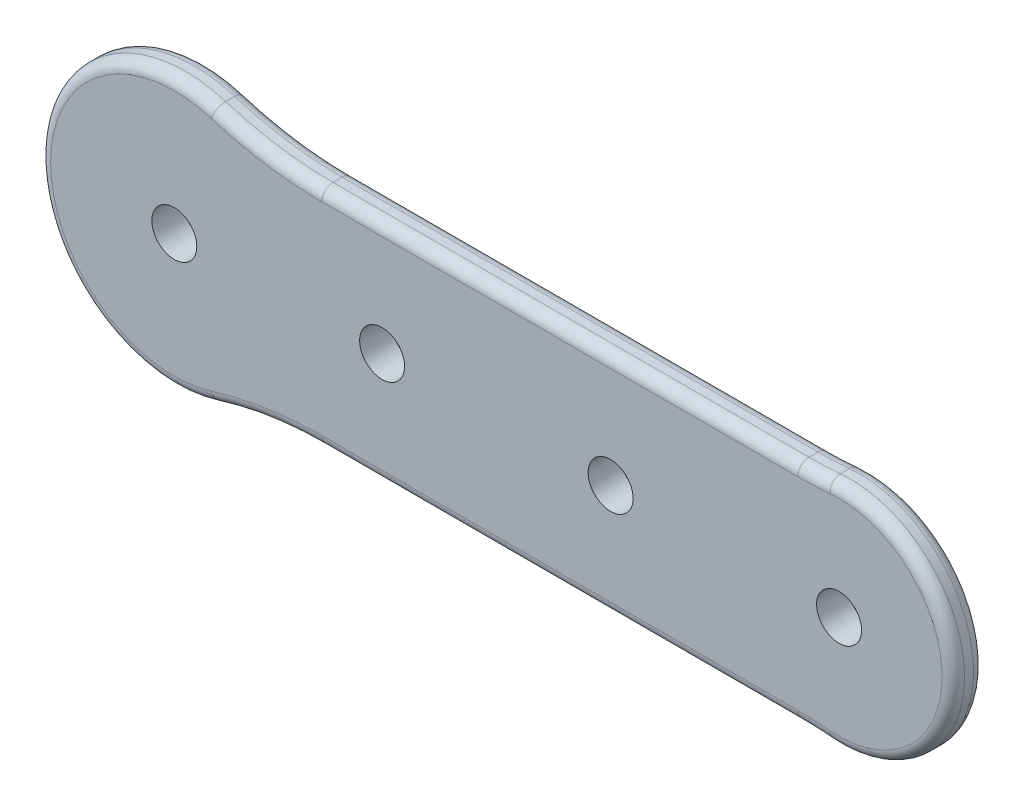
SolidWorks part; units mm, degrees
material "Copper"
ref_plane "Front Plane" through (0, 0, 0) normal (0, 0, 1) x (1, 0, 0)
ref_plane "Top Plane" through (0, 0, 0) normal (0, 1, 0) x (1, 0, 0)
ref_plane "Right Plane" through (0, 0, 0) normal (1, 0, 0) x (0, 0, -1)
sketch "Sketch1" plane through (0, 0, 0) normal (0, 0, 1) x (1, 0, 0)
  line L1 (-73.9, 25) -> (73.9, 25)
  line L2 (-73.9, 25) -> (-73.9, -25)
  line L3 (-73.9, -25) -> (73.9, -25)
  line L4 (73.9, 25) -> (73.9, -25)
  line L5 (-73.9, 25) -> (73.9, -25) construction
  line L6 (-73.9, -25) -> (73.9, 25) construction
  circle A0 centre (-73.9, 0) radius 30
  circle A1 centre (73.9, 0) radius 25.4
  circle A2 centre (73.9, 0) radius 5
  circle A3 centre (-73.9, 0) radius 5
  circle A4 centre (23.1, 0) radius 5
  circle A5 centre (-27.7, 0) radius 5
  point P0 (0, 0)
  point P10 (99.3, 0)
  point P11 (-103.9, 0)
  dimension "D1" = 50.8
  dimension "D2" = 60
  dimension "D5" = 50.8
  dimension "D6" = 50.8
  dimension "D7" = 10
  dimension "D8" = 10
  dimension "D9" = 10
  dimension "D10" = 10
  dimension "D3" = 50
  dimension "D4" = 203.2
extrude "Boss-Extrude1" add sketch "Sketch1" along normal blind 7 contours A1 L1 A0 L3 A5 A4 | A2 L4 L3 A1 L1 | A2 L4 L1 A1 L3 | A3 L2 L3 A0 L1 | A3 L2 L1 A0 L3 region at (-85.4726, 0, 0) region at (-60.2632, 0, 0) region at (3.1364, 0, 0) region at (84.9976, 0, 0) region at (62.7476, 0, 0)
fillet "Fillet1" radius 80 4 edges at (69.41, -25, 3.5) (69.41, 25, 3.5) (-57.3169, -25, 3.5) (-57.3169, 25, 3.5)
fillet "Fillet2" radius 2.5 16 edges at (-53.1733, 25.9143, 7) (-103.9, 0, 7) (-53.1733, -25.9143, 7) (11.8067, -25, 7) (68.211, -25.0759, 7) (99.3, 0, 7) (68.211, 25.0759, 7) (-53.1733, 25.9143, 0) (-103.9, 0, 0) (-53.1733, -25.9143, 0) (11.8067, -25, 0) (68.211, -25.0759, 0) (99.3, 0, 0) (68.211, 25.0759, 0) (11.8067, 25, 7) (11.8067, 25, 0)
